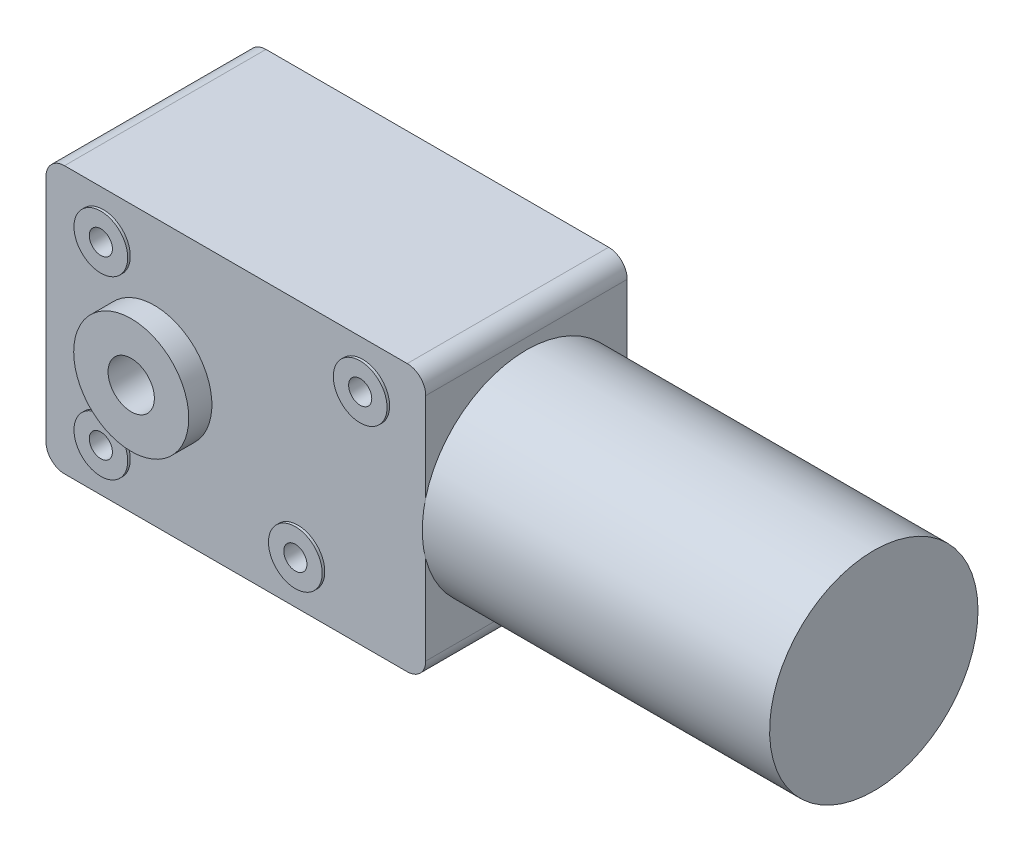
SolidWorks part; units mm, degrees
ref_plane "정면" through (0, 0, 0) normal (0, 0, 1) x (1, 0, 0)
ref_plane "윗면" through (0, 0, 0) normal (0, 1, 0) x (1, 0, 0)
ref_plane "우측면" through (0, 0, 0) normal (1, 0, 0) x (0, 0, -1)
sketch "스케치2" plane through (0, 0, 0) normal (0, 0, 1) x (1, 0, 0)
  line L1 (-37, 28.82) -> (37, 28.82)
  line L2 (-41, 24.82) -> (-41, -24.82)
  line L3 (-37, -28.82) -> (37, -28.82)
  line L4 (41, 24.82) -> (41, -24.82)
  line L5 (-41, 28.82) -> (41, -28.82) construction
  line L6 (-41, -28.82) -> (41, 28.82) construction
  arc A0 (37, 28.82) -> (41, 24.82) centre (37, 24.82) cw
  arc A1 (37, -28.82) -> (41, -24.82) centre (37, -24.82) ccw
  arc A2 (-41, -24.82) -> (-37, -28.82) centre (-37, -24.82) ccw
  arc A3 (-37, 28.82) -> (-41, 24.82) centre (-37, 24.82) ccw
  point P0 (0, 0)
  dimension "D3" = 4
  dimension "D1" = 57.64
  dimension "D2" = 82
extrude "보스-돌출1" add sketch "스케치2" along normal blind 43.5
sketch "스케치3" plane through (0, 0, 43.5) normal (0, 0, 1) x (1, 0, 0)
  line L0 (-41, 24.82) -> (-41, -24.82) construction
  line L1 (37, 28.82) -> (-37, 28.82) construction
  circle A0 centre (-17.6, 0) radius 12.42
  circle A1 centre (-17.6, 0) radius 5
  circle A2 centre (-28.6, 19) radius 5.8
  circle A3 centre (-28.6, -19) radius 5.8
  circle A4 centre (27.4, 19) radius 5.8
  circle A5 centre (13.4, -19) radius 5.8
  circle A6 centre (-28.6, 19) radius 2.5
  circle A7 centre (27.4, 19) radius 2.5
  circle A8 centre (13.4, -19) radius 2.5
  circle A9 centre (-28.6, -19) radius 2.5
  dimension "D1" = 11.6
  dimension "D3" = 11.6
  dimension "D4" = 11.6
  dimension "D6" = 11.6
  dimension "D12" = 10
  dimension "D13" = 24.84
  dimension "D14" = 5
  dimension "D15" = 5
  dimension "D16" = 5
  dimension "D17" = 5
  dimension "D2" = 56
  dimension "D5" = 12.4
  dimension "D7" = 42
  dimension "D8" = 38
  dimension "D9" = 9.82
  dimension "D10" = 23.4
  dimension "D11" = 28.82
extrude "보스-돌출2" add sketch "스케치3" along normal blind 0.5575 contours A2 A6 | A3 A9 | A5 A8 | A4 A7 region at (-34.236, 19, 43.5) region at (-34.236, -19, 43.5) region at (21.764, 19, 43.5) region at (7.764, -19, 43.5)
extrude "보스-돌출3" add sketch "스케치3<3>" along normal blind 5 contours A0 A1 region at (-29.6687, 0, 43.5)
sketch "스케치3<3>" plane through (0, 0, 43.5) normal (0, 0, 1) x (1, 0, 0) same geometry as "스케치3"
sketch "스케치4" plane through (41, 0, 0) normal (1, 0, 0) x (0, 0, -1)
  line L0 (0, -24.82) -> (0, 24.82) construction
  circle A0 centre (-21.75, 0) radius 22.5
  dimension "D1" = 45
  dimension "D2" = 21.75
extrude "보스-돌출4" add sketch "스케치4" along normal blind 75
extrude "컷-돌출1" cut sketch "스케치3<4>" against normal blind 10 contours A1 region at (-17.6, 0, 43.5)
sketch "스케치3<4>" plane through (0, 0, 43.5) normal (0, 0, 1) x (1, 0, 0) same geometry as "스케치3"
sketch "스케치5" plane through (0, 0, 43.5) normal (0, 0, 1) x (1, 0, 0)
  circle A0 centre (27.4, 19) radius 2.5
  circle A1 centre (13.4, -19) radius 2.5
  circle A2 centre (-28.6, -19) radius 2.5
  circle A3 centre (-28.6, 19) radius 2.5
extrude "컷-돌출2" cut sketch "스케치5" against normal blind 10
ref_plane "평면1" through (0, 0, 21.75) normal (0, 0, 1) x (1, 0, 0)
mirror "대칭 복사1" about plane through (0, 0, 21.75) normal (0, 0, 1) of "컷-돌출2", "보스-돌출2"
